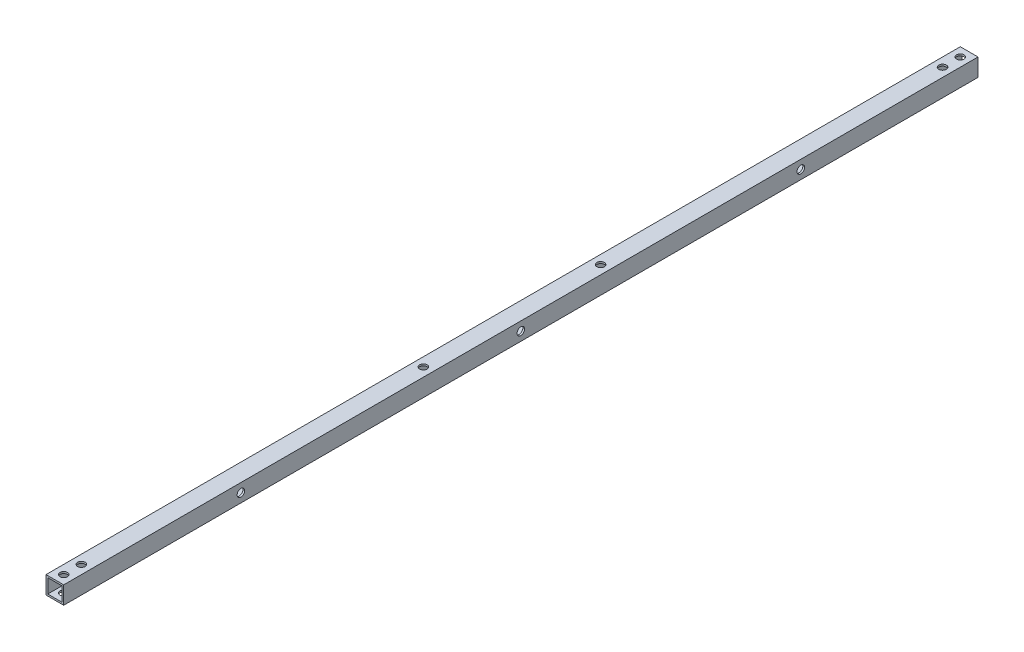
SolidWorks part; units mm, degrees
ref_plane "Front Plane" through (0, 0, 0) normal (0, 0, 1) x (1, 0, 0)
ref_plane "Top Plane" through (0, 0, 0) normal (0, 1, 0) x (1, 0, 0)
ref_plane "Right Plane" through (0, 0, 0) normal (1, 0, 0) x (0, 0, -1)
sketch "Sketch1" plane through (0, 0, 0) normal (0, 0, 1) x (1, 0, 0)
  line L0 (0, 0) -> (10, 0)
  line L1 (0, 0) -> (0, 10)
  line L2 (0, 10) -> (10, 10)
  line L3 (10, 0) -> (10, 10)
  line L4 (1, 9) -> (9, 9)
  line L5 (1, 9) -> (1, 1)
  line L6 (1, 1) -> (9, 1)
  line L7 (9, 9) -> (9, 1)
  dimension "D1" = 10
  dimension "D2" = 10
  dimension "D3" = 8
  dimension "D4" = 8
  dimension "D5" = 1
  dimension "D6" = 1
  dimension "D7" = 0
extrude "Boss-Extrude1" add sketch "Sketch1" along normal blind 516
sketch "Sketch2" plane through (0, 10, 0) normal (0, 1, 0) x (1, 0, 0)
  line L0 (10, -516) -> (10, 0) construction
  line L1 (10, 0) -> (0, 0) construction
  line L2 (10, -516) -> (0, -516) construction
  circle A0 centre (5, -5) radius 2.125
  circle A1 centre (5, -15) radius 2.125
  circle A2 centre (5, -501) radius 2.125
  circle A3 centre (5, -511) radius 2.125
  dimension "D1" = 4.25
  dimension "D2" = 4.25
  dimension "D7" = 4.25
  dimension "D8" = 4.25
  dimension "D3" = 5
  dimension "D4" = 5
  dimension "D5" = 5
  dimension "D6" = 15
  dimension "D9" = 5
  dimension "D10" = 5
  dimension "D11" = 5
  dimension "D12" = 15
extrude "Cut-Extrude1" cut sketch "Sketch2" against normal blind 116
sketch "Sketch3" plane through (0, 0, 0) normal (0, -1, 0) x (1, 0, 0)
  line L0 (10, 516) -> (10, 0) construction
  line L1 (0, 516) -> (10, 516) construction
  line L2 (0, 0) -> (10, 0) construction
  circle A0 centre (5, 308) radius 2.125
  circle A1 centre (5, 208) radius 2.125
  dimension "D1" = 4.25
  dimension "D2" = 5
  dimension "D3" = 208
  dimension "D4" = 4.25
  dimension "D5" = 5
  dimension "D6" = 208
extrude "Cut-Extrude2" cut sketch "Sketch3" against normal blind 10
sketch "Sketch4" plane through (10, 0, 0) normal (1, 0, 0) x (0, 0, -1)
  line L0 (0, 0) -> (0, 10) construction
  line L1 (-516, 0) -> (-516, 10) construction
  line L2 (-516, 0) -> (0, 0) construction
  circle A0 centre (-416, 5) radius 2.125
  circle A1 centre (-100, 5) radius 2.125
  circle A2 centre (-258, 5) radius 2.125
  dimension "D1" = 4.25
  dimension "D2" = 4.25
  dimension "D5" = 4.25
  dimension "D3" = 100
  dimension "D4" = 100
  dimension "D6" = 258
  dimension "D7" = 5
extrude "Cut-Extrude3" cut sketch "Sketch4" against normal blind 10
